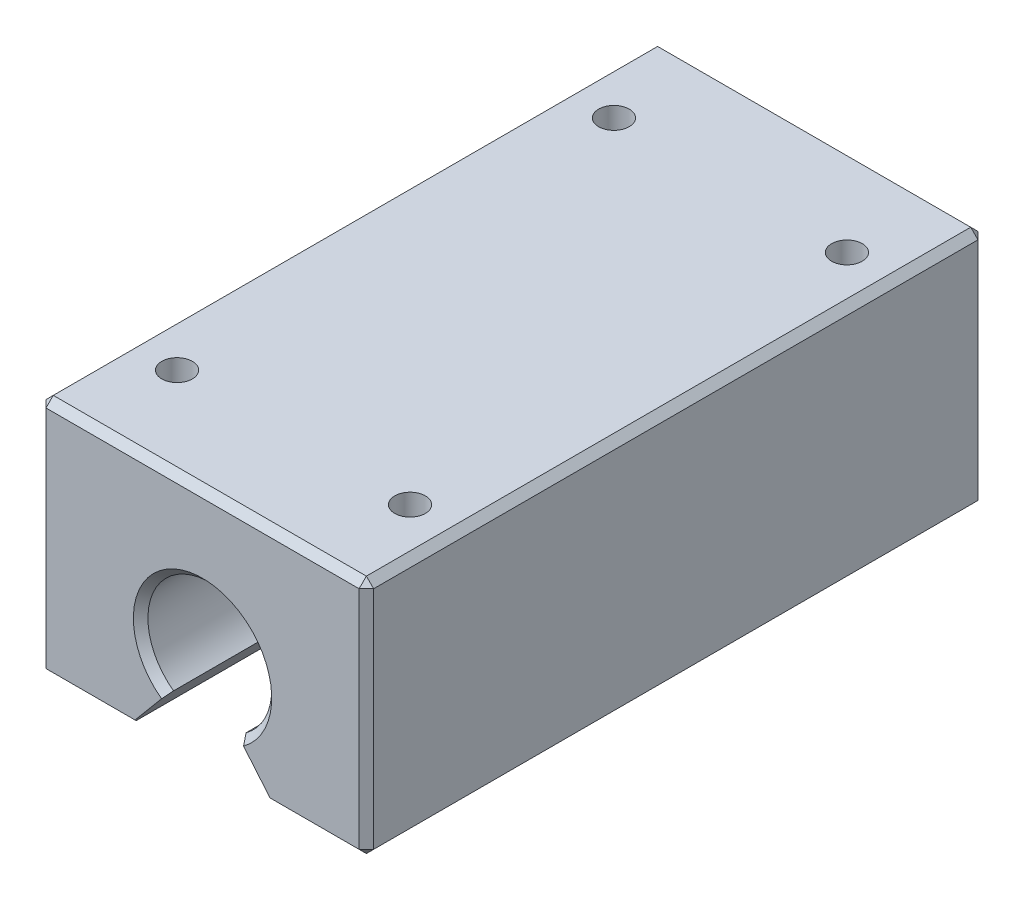
SolidWorks part; units mm, degrees
note: '?' marks a value the reader was unsure of.
material "1060 Alloy"
ref_plane "Front" through (0, 0, 0) normal (0, 0, 1) x (1, 0, 0)
ref_plane "Top" through (0, 0, 0) normal (0, 1, 0) x (1, 0, 0)
ref_plane "Right" through (0, 0, 0) normal (1, 0, 0) x (0, 0, -1)
ref_axis "Axis1" through (-84.4107, 0, 0) along (1, 0, 0)?
ref_axis "Axis2" through (0, 64.3378, 0) along (0, -1, 0)?
ref_axis "Axis3" through (0, 0, -102.329) along (0, 0, 1)?
sketch "Sketch1" plane through (0, 0, 0) normal (0, 0, 1) x (1, 0, 0)
  line L1 (-22.5, -16.5) -> (22.5, -16.5)
  line L2 (-22.5, -16.5) -> (-22.5, 16.5)
  line L3 (-22.5, 16.5) -> (22.5, 16.5)
  line L4 (22.5, -16.5) -> (22.5, 16.5)
  line L5 (-22.5, -16.5) -> (22.5, 16.5) construction
  line L6 (-22.5, 16.5) -> (22.5, -16.5) construction
  point P0 (0, 0)
  dimension "D1" = 45
  dimension "D2" = 33
extrude "Extrude1" add sketch "Sketch1" along normal blind 85
sketch "Sketch2" plane through (0, 0, 85) normal (0, 0, 1) x (1, 0, 0)
  line L0 (22.5, 16.5) -> (-22.5, 16.5) construction
  line L1 (0, -4.4474) -> (-13.5396, -20.5832)
  line L2 (-13.5396, -20.5832) -> (13.5396, -20.5832)
  line L3 (13.5396, -20.5832) -> (0, -4.4474)
  line L4 (-22.5, 16.5) -> (-22.5, -16.5) construction
  line L5 (5, -4.1137) -> (5, -15.1699) construction
  line L6 (-5, -4.1137) -> (-5, -15.1699) construction
  line L7 (-5, -4.1137) -> (0, -4.1137) construction
  line L8 (0, -4.1137) -> (5, -4.1137) construction
  circle A0 centre (0, -3.5) radius 8.5
  point P6 (-22.5, 0)
  line M4 (-22.5, -16.5) -> (22.5, -16.5)
  dimension "D1" = 17
  dimension "D2" = 20
  dimension "D3" = 80
  dimension "D4" = 22.5
  dimension "D5" = 5
extrude "Extrude3" cut sketch "Sketch2" against normal through all contours L3 A0 L1 | L1 A0 L3 | L2 L3 L1 M4 | A0 L1 L3 M4
hole_wizard "M5 Tapped Hole1" positions "Sketch4" profile "Sketch3" tap size "M5" standard "ISO"
sketch "Sketch4" plane through (0, 16.5, 0) normal (0, 1, 0) x (-1, 0, 0)
  line L1 (16, 0.1308) -> (16, 92.3416) construction
  line L4 (-16, 4.1131) -> (-16, 96.4582) construction
  line L7 (16, 12.5) -> (-26.0273, 12.5) construction
  line L13 (16, 72.5) -> (-21.414, 72.5) construction
  line L17 (22.5, 85) -> (22.5, 0) construction
  line L19 (27.4015, 42.5) -> (-26.0273, 42.5) construction
  point P0 (16, 12.5)
  point P1 (-16, 12.5)
  point P3 (-16, 72.5)
  point P5 (16, 72.5)
  dimension "D1" = 60
  dimension "D2" = 30
  dimension "D3" = 32
  dimension "D4" = 6.5
sketch "Sketch3" plane through (-16, 16.5, 12.5) normal (1, 0, 0) x (0, 0, 1)
  line L0 (0, 0) -> (0, 11.2618)
  line L1 (0, 11.2618) -> (2.1, 10)
  line L2 (2.1, 10) -> (2.1, 0)
  line L5 (2.1, 0) -> (0, 0)
  line L10 (0, 11.2618) -> (-2.1, 10) construction
  line L11 (0, -6.35) -> (0, 107.95) construction
  dimension "Tap Drill Dia." = 4.2
  dimension "Tap Drill Depth" = 10
  dimension "Drill Angle" = 118
cosmetic thread "Hole Thread1" parameters "D1"=9, "D2"=5
cosmetic thread "Hole Thread2" parameters "D1"=9, "D2"=5
cosmetic thread "Hole Thread3" parameters "D1"=9, "D2"=5
cosmetic thread "Hole Thread4" parameters "D1"=9, "D2"=5
chamfer "Chamfer1" distance 1 angle 45 16 edges at (0, 5, 0) (0, 5, 85) (16.3067, -16.5, 85) (-16.3067, -16.5, 85) (-22.5, -16.5, 42.5) (-16.3067, -16.5, 0) (22.5, -16.5, 42.5) (16.3067, -16.5, 0) (-22.5, 0, 0) (0, 16.5, 0) (-22.5, 0, 85) (22.5, 0, 85) (-22.5, 16.5, 42.5) (0, 16.5, 85) (22.5, 16.5, 42.5) (22.5, 0, 0)
